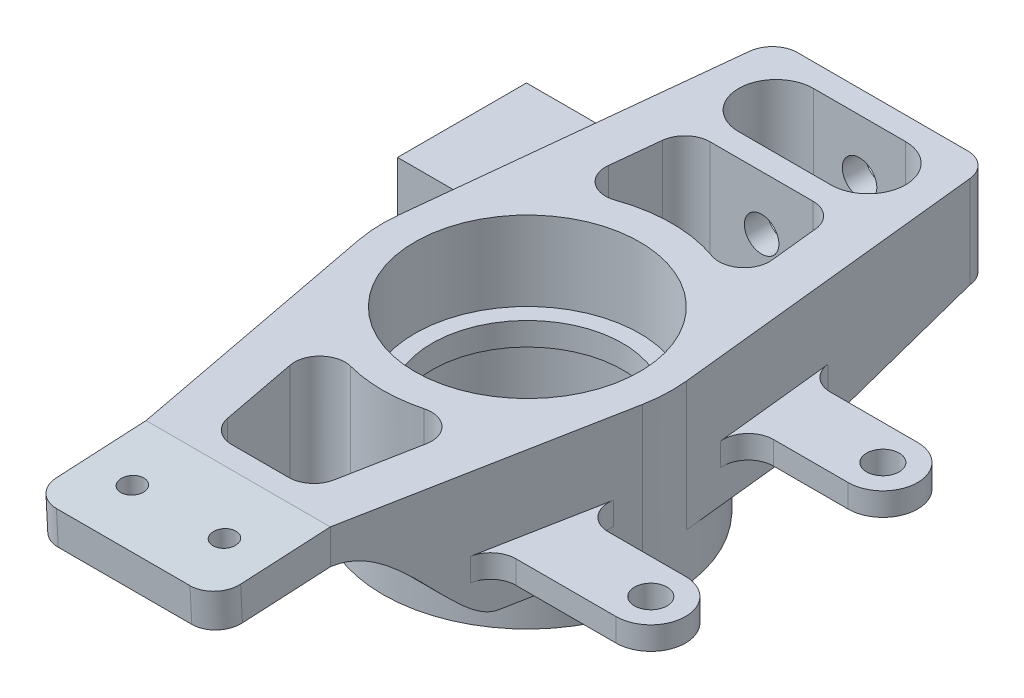
SolidWorks part; units mm, degrees
material "6061-T6 (SS)"
ref_plane "Front Plane" through (0, 0, 0) normal (0, 0, 1) x (1, 0, 0)
ref_plane "Top Plane" through (0, 0, 0) normal (0, 1, 0) x (1, 0, 0)
ref_plane "Right Plane" through (0, 0, 0) normal (1, 0, 0) x (0, 0, -1)
sketch "UBJ LBJ Geometry" plane through (0, 0, 0) normal (1, 0, 0) x (0, 0, -1)
  line L0 (0, 0) -> (0, -97.4059) construction
  line L1 (0, 0) -> (-30.7529, 0) construction
  line L2 (0, 22) -> (-45.5659, 22) construction
  line L3 (0, -10.5425) -> (-23.1063, -10.5425) construction
  line L4 (-94.107, -51.66) -> (81.28, -25.498) construction
  line L5 (50.8, 0) -> (50.8, -88.2735) construction
  circle A0 centre (-94.107, -51.66) radius 10.3251 construction
  circle A1 centre (81.28, -25.498) radius 10.3251 construction
  dimension "D7" = 20.6502
  dimension "D8" = 20.6502
  dimension "D1" = 22
  dimension "D2" = 32.5425
  dimension "D3" = 47.498
  dimension "D4" = 73.66
  dimension "D5" = 94.107
  dimension "D6" = 81.28
  dimension "D9" = 50.8
ref_plane "Wheel Face " through (0, 22, 0) normal (0, -1, 0) x (-1, 0, 0)
ref_plane "Upright Face" through (0, -10.5425, 0) normal (0, -1, 0) x (-1, 0, 0)
ref_plane "Tie Bracket Plane" through (0, 0, -50.8) normal (0, 0, 1) x (1, 0, 0)
sketch "Tie Bracket Geometry" plane through (0, 0, -50.8) normal (0, 0, 1) x (1, 0, 0)
  line L0 (0, -30.0446) -> (-60.5599, -53.6559) construction
  line L4 (0, 200000) -> (0, -200097.4059) construction
  circle A0 centre (-60.5599, -53.6559) radius 8.948 construction
  dimension "D1" = 65
  dimension "D2" = 68.7
sketch "Sketch1" plane through (0, 0, 0) normal (0, 0, 1) x (1, 0, 0)
  line L1 (-75.0953, -10.5425) -> (75.0953, -10.5425) construction
  line L2 (-39.878, -10.5425) -> (-39.878, -59.3105)
  line L3 (-39.878, -59.3105) -> (-32.258, -59.3105)
  line L4 (-32.258, -59.3105) -> (-32.258, -63.1205)
  line L5 (-32.258, -63.1205) -> (-31.0007, -63.1205)
  line L8 (-31.0007, -10.5425) -> (-31.0007, -32.3865)
  line L9 (-31.0007, -32.3865) -> (-26.289, -32.3865)
  line L10 (-26.289, -32.3865) -> (-26.289, -38.7365)
  line L11 (-26.289, -38.7365) -> (-31.0007, -38.7365)
  line L12 (-31.0007, -38.7365) -> (-31.0007, -63.1205)
  line L15 (-39.878, -10.5425) -> (-31.0007, -10.5425)
  line L17 (0, 0) -> (0, -23.5057) construction
  dimension "D1" = 6.35
  dimension "D2" = 62.0014
  dimension "D3" = 24.384
  dimension "D4" = 52.578
  dimension "D5" = 21.844
  dimension "D6" = 48.768
  dimension "D7" = 79.756
  dimension "D8" = 64.516
revolve "Bearing Housing Revolve" add sketch "Sketch1" angle 360 about L17
fillet "Bearing Housing Fillet" radius 6.35 1 edges at (0, -59.3105, 32.258)
sketch "Sketch2" plane through (0, -10.5425, 0) normal (0, -1, 0) x (-1, 0, 0)
  line L3 (39.878, -40.64) -> (39.878, 0)
  line L4 (-39.878, -40.64) -> (-39.878, 0)
  line L5 (39.878, -40.64) -> (-39.878, -40.64)
  circle A4 centre (0, 0) radius 39.878 construction
  arc A5 (39.878, 0) -> (-39.878, 0) centre (0, 0) cw
  dimension "D1" = 40.64
extrude "UBJ Prep" add sketch "Sketch2" along normal blind 35.56
sketch "Sketch3" plane through (-39.878, 0, 0) normal (-1, 0, 0) x (0, 0, 1)
  line L0 (-120.7672, 22) -> (120.7672, 22) construction
  line L1 (40.64, -10.5425) -> (79.7292, -10.5425)
  line L2 (79.7292, -10.5425) -> (111.4357, -12.2041)
  line L3 (111.4357, -12.2041) -> (110.9372, -21.7161)
  line L4 (110.9372, -21.7161) -> (79.2307, -20.0544)
  line L6 (40.64, -46.1025) -> (40.64, -10.5425)
  line L7 (79.7292, -10.5425) -> (79.2307, -20.0544) construction
  line L8 (95.6471, -22.2727) -> (94.107, -51.66) construction
  line L10 (40.64, -46.1025) -> (50.8, -46.1025) construction
  line L11 (50.8, -46.1025) -> (63.5, -20.0544) construction
  line L12 (63.5, -20.0544) -> (79.2307, -20.0544) construction
  circle A0 centre (94.107, -51.66) radius 13.6189 construction
  spline S0 degree 3 poles (40.64, -46.1025) (50.8, -46.1025) (63.5, -20.0544) (79.2307, -20.0544) knots 0 0 0 0 1 1 1 1
  dimension "D1" = 73.66
  dimension "D2" = 94.107
  dimension "D3" = 9.525
  dimension "D4" = 31.75
  dimension "D5" = 3
  dimension "D6" = 15.24
  dimension "D8" = 50.8
  dimension "D9" = 63.5
extrude "UBJ Extrude " add sketch "Sketch3" against normal up to surface (79.756 mm away) up to face at (39.878, -28.3225, 20.32)
sketch "Sketch4" plane through (0, -15.8586, -0.8311) normal (0, -0.9986, -0.0523) x (1, 0, 0)
  line L0 (0, 111.9217) -> (0, 27.8969) construction
  line L1 (39.878, 111.9217) -> (-39.878, 111.9217) construction
  line L3 (-12.7, 96.6817) -> (12.7, 96.6817) construction
  circle A0 centre (-12.7, 96.6817) radius 3.175
  circle A1 centre (12.7, 96.6817) radius 3.175
  point P8 (0, 96.6817)
  dimension "D2" = 6.35
  dimension "D1" = 25.4
  dimension "D3" = 15.24
extrude "Camber Block Holes" cut sketch "Sketch4" against normal up to surface (9.525 mm away) up to face at (0, -11.3733, 95.5825)
sketch "Sketch5" plane through (0, -46.1025, 0) normal (0, -1, 0) x (1, 0, 0)
  line L0 (-25.4, 110.9372) -> (-25.4, 79.6952)
  line L1 (25.4, 111.4357) -> (39.878, 111.4357)
  line L2 (39.878, 110.9372) -> (-39.878, 110.9372) construction
  line L4 (-25.4, 79.6952) -> (-39.1722, 7.4695)
  line L5 (25.4, 110.9372) -> (25.4, 79.6952)
  line L6 (25.4, 79.6952) -> (39.1722, 7.4695)
  line L7 (-25.4, 110.9372) -> (-25.4, 111.4357)
  line L8 (39.878, 111.4357) -> (-39.878, 111.4357) construction
  line L9 (25.4, 110.9372) -> (25.4, 111.4357)
  line L10 (-25.4, 111.4357) -> (-39.878, 111.4357)
  line L11 (-39.878, 111.4357) -> (-39.878, 0)
  line L12 (39.878, 111.4357) -> (39.878, 0)
  line L13 (-13.622, 73.66) -> (13.622, 73.66)
  line L14 (-13.622, 73.66) -> (-21.2309, 33.7565)
  line L15 (13.622, 73.66) -> (21.2309, 33.7565)
  arc A0 (-39.878, 0) -> (-39.1722, 7.4695) centre (0, 0) cw
  circle A1 centre (0, 0) radius 39.878 construction
  arc A2 (39.878, 0) -> (-39.878, 0) centre (0, 0) ccw construction
  arc A3 (39.878, 0) -> (39.1722, 7.4695) centre (0, 0) ccw
  arc A4 (-21.2309, 33.7565) -> (21.2309, 33.7565) centre (0, 0) cw
  point P31 (0, 73.66)
  dimension "D1" = 25.4
  dimension "D2" = 12.7
  dimension "D3" = 31.242
  dimension "D4" = 73.66
extrude "Weight Saving" cut sketch "Sketch5" against normal through all
fillet "Fillet2" radius 6.985 4 edges at (21.2309, -28.3225, 33.7565) (-21.2309, -28.3225, 33.7565) (13.622, -15.823, 73.66) (-13.622, -15.823, 73.66)
sketch "Sketch6" plane through (0, -10.5425, 0) normal (0, -1, 0) x (-1, 0, 0)
  line L0 (-39.878, 0) -> (-39.878, 40.64)
  line L1 (-39.878, 40.64) -> (39.878, 40.64)
  line L2 (39.878, 40.64) -> (39.878, 0)
  circle A0 centre (0, 0) radius 39.878 construction
  arc A1 (-39.878, 0) -> (39.878, 0) centre (0, 0) cw
  dimension "D1" = 40.64
extrude "LBJ Prep" add sketch "Sketch6" along normal blind 35.56
sketch "Sketch8" plane through (-39.878, 0, 0) normal (-1, 0, 0) x (0, 0, 1)
  line L0 (-40.64, -10.5425) -> (-97.9551, -10.5425)
  line L1 (-97.9551, -10.5425) -> (-97.9551, -35.9425)
  line L2 (-97.9551, -35.9425) -> (-91.6051, -35.9425)
  line L7 (-40.64, -46.1025) -> (-40.64, -10.5425)
  line L8 (-120.7672, 22) -> (120.7672, 22) construction
  line L9 (-91.6051, -35.9425) -> (-91.6051, -10.5425) construction
  line L10 (-91.6051, -35.9425) -> (-40.64, -46.1025)
  circle A0 centre (-81.28, -25.498) radius 10.3251 construction
  dimension "D3" = 20.6502
  dimension "D1" = 81.28
  dimension "D2" = 47.498
  dimension "D4" = 6.35
  dimension "D5" = 25.4
extrude "LBJ Area " add sketch "Sketch8" against normal up to surface (79.756 mm away) up to face at (39.878, -28.3225, -20.32)
sketch "Sketch7" plane through (0, -46.1025, 0) normal (0, -1, 0) x (1, 0, 0)
  line L0 (-12.7, -81.28) -> (12.7, -81.28) construction
  line L1 (0, -200000) -> (0, 200045.5659) construction
  line L2 (-12.7, -70.9549) -> (12.7, -70.9549)
  line L3 (-12.7, -91.6051) -> (12.7, -91.6051)
  line L4 (-29.718, -97.9551) -> (-39.6558, -4.2036)
  line L5 (39.878, -97.9551) -> (-39.878, -97.9551) construction
  line L6 (29.718, -97.9551) -> (39.6558, -4.2036)
  line L7 (-29.718, -97.9551) -> (-39.878, -97.9551)
  line L8 (-39.878, -97.9551) -> (-39.878, 0)
  line L9 (29.718, -97.9551) -> (39.878, -97.9551)
  line L10 (39.878, -97.9551) -> (39.878, 0)
  line L13 (-20.482, -64.6049) -> (20.482, -64.6049)
  line L14 (20.482, -64.6049) -> (23.9504, -31.8847)
  line L15 (-20.482, -64.6049) -> (-23.9504, -31.8847)
  arc A0 (-12.7, -70.9549) -> (-12.7, -91.6051) centre (-12.7, -81.28) ccw
  arc A1 (12.7, -91.6051) -> (12.7, -70.9549) centre (12.7, -81.28) ccw
  circle A2 centre (0, 0) radius 39.878 construction
  arc A3 (-39.878, 0) -> (39.878, 0) centre (0, 0) ccw construction
  arc A4 (39.878, 0) -> (39.6558, -4.2036) centre (0, 0) cw
  arc A5 (-39.878, 0) -> (-39.6558, -4.2036) centre (0, 0) ccw
  arc A6 (-23.9504, -31.8847) -> (23.9504, -31.8847) centre (0, 0) ccw
  point P4 (0, -81.28)
  point P28 (0, -64.6049)
  dimension "D1" = 81.28
  dimension "D2" = 20.6502
  dimension "D3" = 25.4
  dimension "D4" = 10.16
  dimension "D5" = 6.35
  dimension "D6" = 12.7
extrude "LBJ Taper And Slot" cut sketch "Sketch7" against normal up to surface (35.56 mm away) up to face at (0, -10.5425, 31.0007)
fillet "Fillet3" radius 6.985 4 edges at (20.482, -25.9338, -64.6049) (-20.482, -25.9338, -64.6049) (23.9504, -28.3225, -31.8847) (-23.9504, -28.3225, -31.8847)
extrude "LBJ Holes" cut sketch "Sketch9" against normal up to surface (33.3502 mm away) up to face at (0, -25.9338, -64.6049)
sketch "Sketch9" plane through (0, 0, -97.9551) normal (0, 0, -1) x (-1, 0, 0)
  circle A0 centre (0, -25.498) radius 4.7625
  dimension "D2" = 9.525
  dimension "D1" = 25.498
ref_plane "Brake Mounting Plane" through (0, -30.7025, 0) normal (0, 1, 0) x (1, 0, 0)
sketch "Sketch10" plane through (0, -30.7025, 0) normal (0, 1, 0) x (1, 0, 0)
  line L0 (87.9814, 0) -> (161.3053, 0) construction
  line L1 (0, 72.9505) -> (0, 47.1638) construction
  line L2 (66.04, 32) -> (66.04, -32) construction
  line L3 (66.04, 22.42) -> (37.7249, 22.42)
  line L4 (39.6558, 4.2036) -> (29.718, 97.9551) construction
  line L5 (37.7249, 22.42) -> (35.6939, 41.58)
  line L6 (35.6939, 41.58) -> (66.04, 41.58)
  line L7 (66.04, -22.42) -> (36.3214, -22.42)
  line L8 (25.4, -79.6952) -> (39.1722, -7.4695) construction
  line L9 (36.3214, -22.42) -> (32.6679, -41.58)
  line L10 (32.6679, -41.58) -> (66.04, -41.58)
  circle A0 centre (66.04, 32) radius 4.5
  circle A1 centre (66.04, -32) radius 4.5
  arc A2 (66.04, -41.58) -> (66.04, -22.42) centre (66.04, -32) ccw
  arc A3 (66.04, 22.42) -> (66.04, 41.58) centre (66.04, 32) ccw
  point P7 (66.04, 0)
  dimension "D2" = 9
  dimension "D3" = 5.08
  dimension "D4" = 5.08
  dimension "D1" = 64
  dimension "D5" = 66.04
  dimension "D6" = 90
  dimension "D7" = 90
  dimension "D8" = 90
  dimension "D9" = 90
extrude "Brake Mounts" add sketch "Sketch10" against normal blind 6.35
fillet "Fillet4" radius 6.985 4 edges at (36.3214, -33.8775, 22.42) (32.6679, -33.8775, 41.58) (37.7249, -33.8775, -22.42) (35.6939, -33.8775, -41.58)
sketch "Sketch12" plane through (0, 0, -50.8) normal (0, 0, 1) x (1, 0, 0)
  line L0 (0, 3.2946) -> (0, -38.5659) construction
  line L1 (-90.5661, 0) -> (-38.2005, 0) construction
  line L2 (-68.8149, -10.5425) -> (-68.8149, -53.6559)
  line L3 (-52.3049, -10.5425) -> (-52.3049, -53.6559)
  line L4 (-68.8149, -10.5425) -> (-52.3049, -10.5425)
  line L6 (-75.0953, -10.5425) -> (75.0953, -10.5425) construction
  circle A0 centre (-60.5599, -53.6559) radius 3.175
  arc A1 (-68.8149, -53.6559) -> (-52.3049, -53.6559) centre (-60.5599, -53.6559) ccw
  dimension "D1" = 6.35
  dimension "D2" = 5.08
extrude "Initial Toe Bracket" add sketch "Sketch12" along normal blind 17.78 and the other way blind 17.78 separate body
sketch "Sketch13" plane through (-52.3049, 0, 0) normal (1, 0, 0) x (0, 0, -1)
  line L0 (33.02, -25.7825) -> (68.58, -25.7825)
  line L1 (68.58, -53.6559) -> (68.58, -10.5425) construction
  line L2 (68.58, -25.7825) -> (68.58, -38.4825)
  line L3 (33.02, -25.7825) -> (33.02, -38.4825)
  line L5 (33.02, -38.4825) -> (68.58, -38.4825)
  line L6 (33.02, -53.6559) -> (33.02, -10.5425) construction
  line L8 (-75.0953, -10.5425) -> (75.0953, -10.5425) construction
  dimension "D1" = 12.7
  dimension "D2" = 15.24
extrude "Toe Bracket Connection to Upright" add sketch "Sketch13" along normal up to surface (19.4731 mm away) up to face at (-34.1554, -30.8625, -56.0937)
sketch "Sketch14" plane through (0, 0, -68.58) normal (0, 0, -1) x (-1, 0, 0)
  line L0 (52.3049, -25.7825) -> (68.8149, -25.7825)
  line L1 (68.8149, -10.5425) -> (68.8149, -53.6559) construction
  line L2 (68.8149, -25.7825) -> (68.8149, -10.5425)
  line L3 (68.8149, -10.5425) -> (52.3049, -10.5425)
  line L4 (52.3049, -10.5425) -> (52.3049, -25.7825)
extrude "Excess Toe Bracket Cut" cut sketch "Sketch14" against normal up to surface (35.56 mm away) up to face at (-52.5065, -33.1477, -33.02)
sketch "Sketch15" plane through (-68.8149, 0, 0) normal (-1, 0, 0) x (0, 0, 1)
  line L0 (-61.976, -38.4825) -> (-39.624, -38.4825)
  line L1 (-39.624, -38.4825) -> (-39.624, -61.9109)
  line L2 (-68.58, -61.9109) -> (-33.02, -61.9109) construction
  line L3 (-39.624, -61.9109) -> (-61.976, -61.9109)
  line L4 (-61.976, -61.9109) -> (-61.976, -38.4825)
  line L5 (-33.02, -38.4825) -> (-68.58, -38.4825) construction
  line L6 (-50.8, -25.7825) -> (-50.8, -39.109) construction
  line L8 (-33.02, -25.7825) -> (-68.58, -25.7825) construction
  point P9 (-50.8, -25.7825)
  point P11 (-50.8, -38.4825)
  dimension "D1" = 22.352
extrude "Toe Bracket Slot" cut sketch "Sketch15" against normal up to surface (16.51 mm away) up to face at (-52.3049, -46.0692, -50.8)
fillet "Toe Bracket Fillet" radius 6.985 2 edges at (-32.8318, -32.1325, -68.58) (-36.6012, -32.1325, -33.02)
fillet "Fillet5" radius 6.985 4 edges at (-25.4, -16.9601, 111.1865) (25.4, -16.9601, 111.1865) (29.718, -23.2425, -97.9551) (-29.718, -23.2425, -97.9551)
equation "\"Wheel_Offset\"= 22mm"
equation "\"HUB_to_UBJ_Lat\"= 2.9in"
equation "\"Hub_to_UBJ_Vert\"= 3.705in"
equation "\"Hub_to_LBJ_Lat\"= 1.87in"
equation "\"Hub_to_LBJ_Vert\"= 3.2in"
equation "\"Wheel_face_to_Upright_back\"= 1.2812in'This is the distance between the whee face to the upright back."
equation "\"UBJ_Angle\"= 3deg"
equation "\"D2@UBJ LBJ Geometry\" = \"Wheel_face_to_Upright_back\""
equation "\"D3@UBJ LBJ Geometry\" = \"Hub_to_LBJ_Lat\""
equation "\"D4@UBJ LBJ Geometry\" = \"HUB_to_UBJ_Lat\""
equation "\"D5@UBJ LBJ Geometry\" = \"Hub_to_UBJ_Vert\""
equation "\"D6@UBJ LBJ Geometry\" = \"Hub_to_LBJ_Vert\""
equation "\"D1@Sketch3\"=\"HUB_to_UBJ_Lat\""
equation "\"D2@Sketch3\"=\"Hub_to_UBJ_Vert\""
equation "\"D1@Sketch8\"=\"Hub_to_LBJ_Vert\""
equation "\"D2@Sketch8\"=\"Hub_to_LBJ_Lat\""
equation "\"Hub_Tie_Bracket_Vert\"= 2in'(Not Given) Ask Sus and Controls later"
equation "\"Tie_Beta\"= 21.3deg'From FE11 Master "
equation "\"Toe_Arm\"= 65mm'From FE11 Master (Assume Dist start at KPI)"
equation "\"D9@UBJ LBJ Geometry\" = \"Hub_Tie_Bracket_Vert\""
equation "\"D1@Sketch7\"=\"Hub_to_LBJ_Vert\""
equation "\"D1@Sketch9\"=\"Hub_to_LBJ_Lat\"-\"Wheel_Offset\""
equation "\"D1@Tie Bracket Geometry\" = \"Toe_Arm\""
equation "\"D2@Tie Bracket Geometry\" = 90 - \"Tie_Beta\""
equation "\"D5@Sketch3\"=\"UBJ_Angle\""
equation "\"D1@Sketch7\"=\"Hub_to_LBJ_Lat\""
